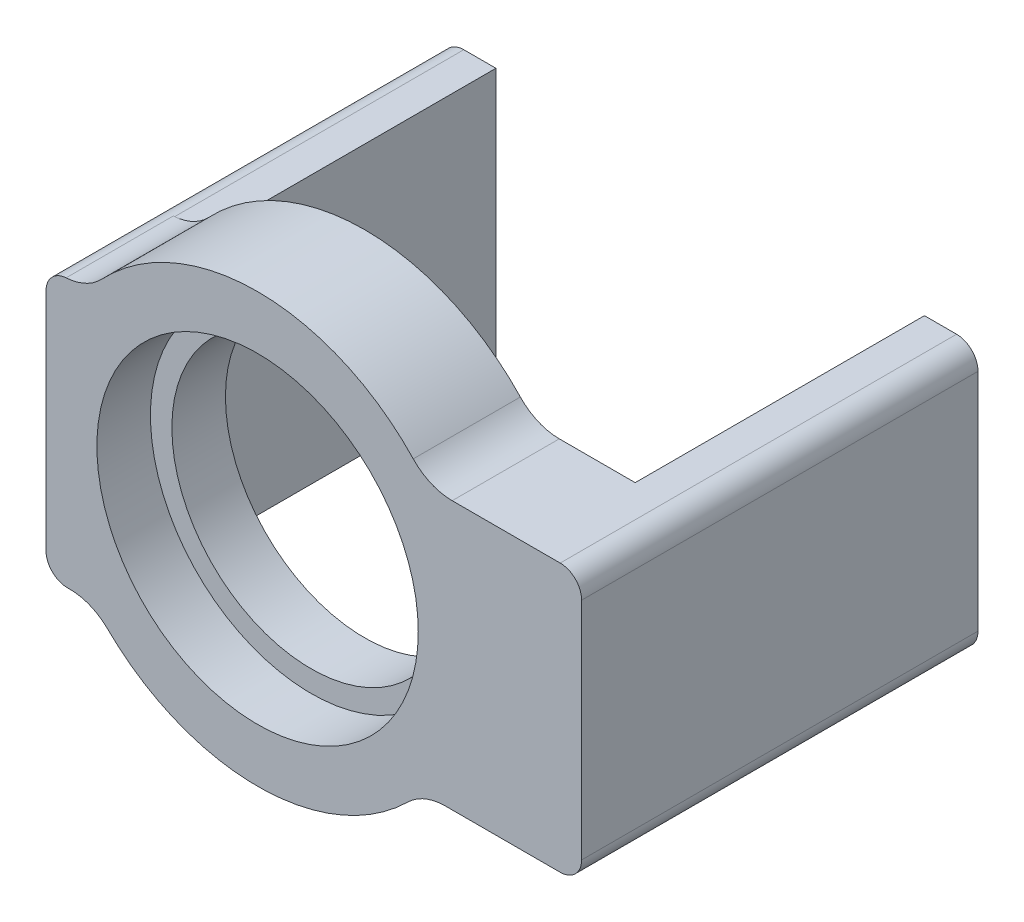
SolidWorks part; units mm, degrees
ref_plane "Front Plane" through (0, 0, 0) normal (0, 0, 1) x (1, 0, 0)
ref_plane "Top Plane" through (0, 0, 0) normal (0, 1, 0) x (1, 0, 0)
ref_plane "Right Plane" through (0, 0, 0) normal (1, 0, 0) x (0, 0, -1)
sketch "Sketch2" plane through (0, 0, 1.8) normal (0, 0, 1) x (1, 0, 0)
  line L5 (-76.5966, -98.699) -> (-81, -98.699)
  line L6 (-77.1172, -73.699) -> (-81, -73.699)
  line L9 (-31, -73.699) -> (-45.3828, -73.699)
  line L10 (-31, -98.699) -> (-45.9034, -98.699)
  line L14 (-31, -73.699) -> (-31, -98.699)
  line L16 (-81, -98.699) -> (-81, -73.699)
  circle A1 centre (-61.25, -85.874) radius 15
  arc A2 (-76.5966, -98.699) -> (-45.9034, -98.699) centre (-61.25, -85.874) ccw
  arc A4 (-45.3828, -73.699) -> (-77.1172, -73.699) centre (-61.25, -85.874) ccw
extrude "Boss-Extrude1" add sketch "Sketch2" against normal blind 5
sketch "Sketch3" plane through (0, 0, -3.2) normal (0, 0, -1) x (-1, 0, 0)
  line L3 (76.5966, -98.699) -> (81, -98.699)
  line L4 (76.5966, -98.699) -> (81, -98.699)
  line L5 (31, -73.699) -> (31, -98.699)
  line L14 (81, -73.699) -> (77.1172, -73.699)
  line L15 (81, -73.699) -> (77.1172, -73.699)
  line L16 (45.3828, -73.699) -> (31, -73.699)
  line L17 (45.3828, -73.699) -> (31, -73.699)
  line L18 (31, -73.699) -> (31, -98.699)
  line L20 (31, -98.699) -> (45.9034, -98.699)
  line L21 (31, -98.699) -> (45.9034, -98.699)
  line L22 (81, -98.699) -> (81, -73.699)
  line L23 (81, -98.699) -> (81, -73.699)
  arc A1 (45.9034, -98.699) -> (76.5966, -98.699) centre (61.25, -85.874) ccw
  arc A2 (45.9034, -98.699) -> (76.5966, -98.699) centre (61.25, -85.874) ccw
  circle A3 centre (61.25, -85.874) radius 13
  arc A6 (77.1172, -73.699) -> (45.3828, -73.699) centre (61.25, -85.874) ccw
  arc A8 (77.1172, -73.699) -> (45.3828, -73.699) centre (61.25, -85.874) ccw
  dimension "D1" = 0
extrude "Boss-Extrude2" add sketch "Sketch3" along normal blind 5
sketch "Sketch6" plane through (0, 0, -8.2) normal (0, 0, -1) x (-1, 0, 0)
  line L0 (81, -73.699) -> (77.1172, -73.699) construction
  line L1 (31, -98.699) -> (36, -98.699)
  line L2 (31, -98.699) -> (31, -73.699)
  line L3 (31, -73.699) -> (36, -73.699)
  line L4 (36, -98.699) -> (36, -73.699)
  line L5 (81, -98.699) -> (76, -98.699)
  line L6 (81, -98.699) -> (81, -73.699)
  line L7 (81, -73.699) -> (76, -73.699)
  line L8 (76, -98.699) -> (76, -73.699)
  line L9 (45.3828, -73.699) -> (31, -73.699) construction
extrude "Boss-Extrude3" add sketch "Sketch6" along normal up to surface (27 mm away)
fillet "Fillet1" radius 2 4 edges at (-31, -73.699, -16.7) (-31, -98.699, -16.7) (-81, -73.699, -16.7) (-81, -98.699, -16.7)
fillet "Fillet2" radius 5 4 edges at (-45.3828, -73.699, -3.2) (-45.9034, -98.699, -3.2) (-77.1172, -73.699, -3.2) (-76.5966, -98.699, -3.2)
